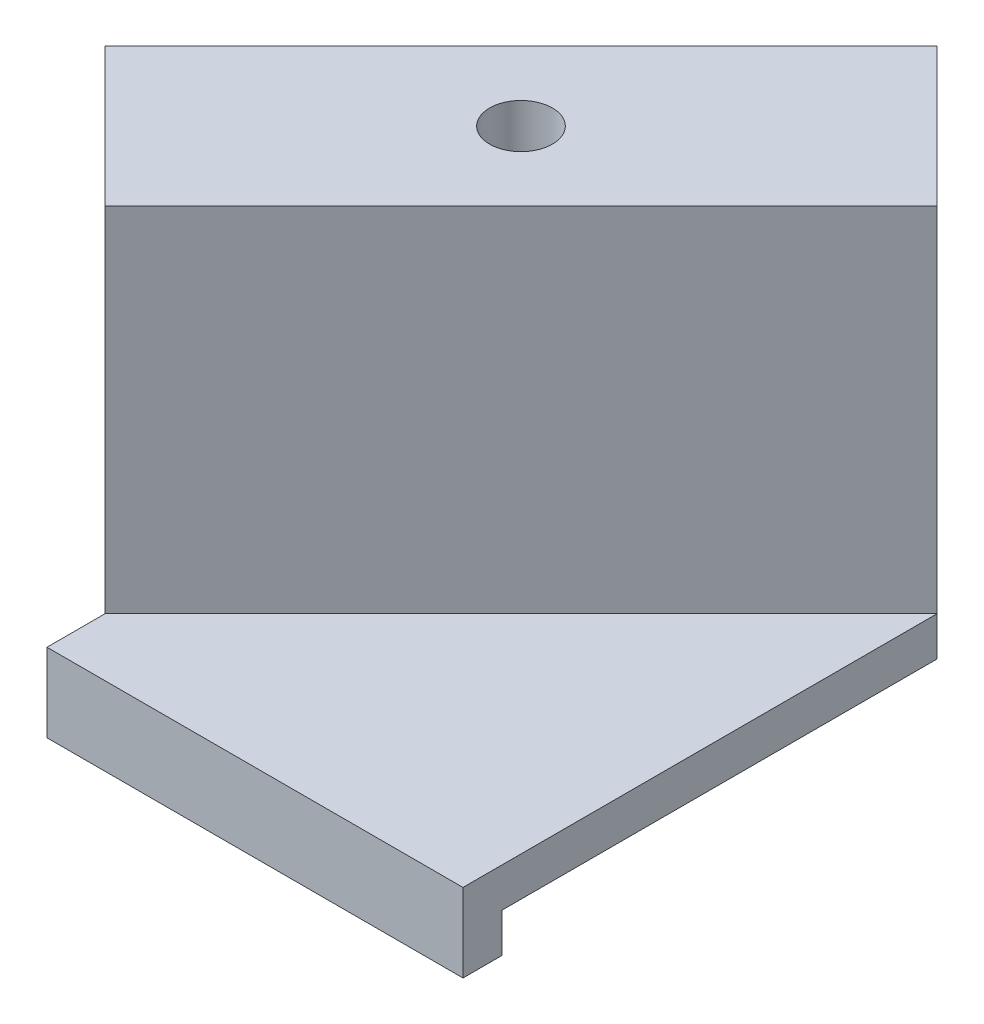
SolidWorks part; units mm, degrees
ref_plane "Front Plane" through (0, 0, 0) normal (0, 0, 1) x (1, 0, 0)
ref_plane "Top Plane" through (0, 0, 0) normal (0, 1, 0) x (1, 0, 0)
ref_plane "Right Plane" through (0, 0, 0) normal (1, 0, 0) x (0, 0, -1)
sketch "Sketch1" plane through (0, 0, 0) normal (0, 1, 0) x (1, 0, 0)
  line L0 (-33.2702, -15) -> (27.677, -15) construction
  line L2 (-7.0711, -14.1421) -> (14.1421, 7.0711)
  line L3 (-7.0711, -14.1421) -> (-14.1421, -7.0711)
  line L4 (-14.1421, -7.0711) -> (7.0711, 14.1421)
  line L5 (14.1421, 7.0711) -> (7.0711, 14.1421)
  line L6 (-7.0711, -14.1421) -> (7.0711, 14.1421) construction
  line L7 (-14.1421, -7.0711) -> (14.1421, 7.0711) construction
  line L8 (14.1421, 7.0711) -> (14.1421, -15.1)
  line L9 (14.1421, -15.1) -> (-8.0289, -15.1)
  line L10 (-7.0711, -14.1421) -> (-7.0711, -17.1)
  line L11 (-7.0711, -17.1) -> (14.1421, -17.1)
  line L12 (14.1421, -17.1) -> (14.1421, -15.1)
  circle A0 centre (0, 0) radius 1.6
  point P5 (-8.0289, -15.1)
  dimension "D1" = 3.2
  dimension "D2" = 15
  dimension "D3" = 30
  dimension "D4" = 10
  dimension "D5" = 45
  dimension "D6" = 2
  dimension "D7" = 0.1
extrude "Boss-Extrude1" add sketch "Sketch1" along normal blind 20 contours L2 L5 L4 L3 A0 region at (-10.3238, 0, 10.3238)
extrude "Boss-Extrude2" add sketch "Sketch1<3>" along normal blind 2 contours L9 L8 L2 region at (6.7782, 0, 7.6964)
sketch "Sketch1<3>" plane through (0, 0, 0) normal (0, 1, 0) x (1, 0, 0) same geometry as "Sketch1"
extrude "Boss-Extrude3" add sketch "Sketch1<4>" along normal blind 2 and the other way blind 2 contours L11 L12 L9 L10 region at (3.5355, 0, 16.1)
sketch "Sketch1<4>" plane through (0, 0, 0) normal (0, 1, 0) x (1, 0, 0) same geometry as "Sketch1"
